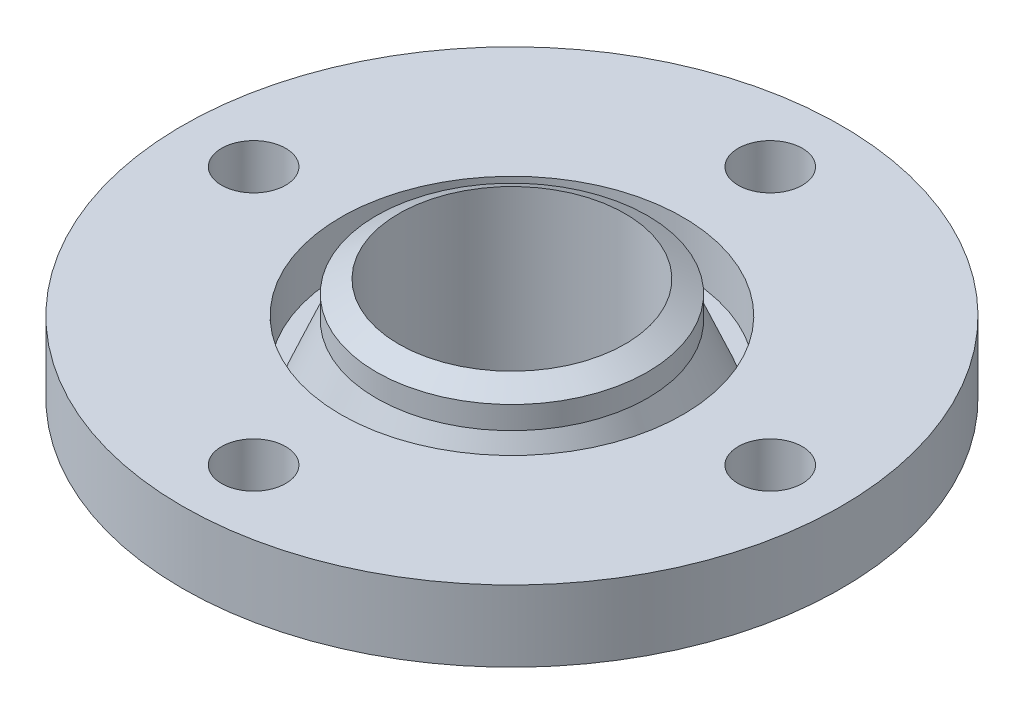
SolidWorks part; units mm, degrees
revolve "基体-旋转" add sketch "1" angle 360 about L0
sketch "1" plane through (0, 0, 0) normal (0, 0, 1) x (1, 0, 0)
  line L0 (0, 0) -> (0, -80.3134) construction
  line L1 (-31.75, 0) -> (-31.75, -45)
  line L2 (-31.75, -45) -> (-59, -45)
  line L3 (-59, -45) -> (-59, -29)
  line L4 (-59, -29) -> (-92.5, -29)
  line L5 (-92.5, -29) -> (-92.5, -9)
  line L6 (-92.5, -9) -> (-48, -9)
  line L7 (-48, -9) -> (-48, -23)
  line L8 (-48, -23) -> (-54, -29)
  line L9 (-54, -29) -> (-46, -29)
  line L10 (-46, -29) -> (-38.05, -10)
  line L11 (-38.05, -10) -> (-38.05, -3.6373)
  line L12 (92.5, -29) -> (92.5, -9) construction
  line L13 (59, -45) -> (59, -29) construction
  line L14 (-38.05, -3.6373) -> (-31.75, 0)
  line L15 (38.05, -10) -> (38.05, -3.6373) construction
  line L16 (46, -29) -> (38.05, -10) construction
  line L17 (48, -9) -> (48, -23) construction
  dimension "A1" = 76.1
  dimension "B1" = 96
  dimension "C" = 20
  dimension "DD" = 118
  dimension "D" = 185
  dimension "F" = 16
  dimension "D7" = 45
  dimension "E" = 6
  dimension "S" = 6.3
  dimension "H1" = 10
  dimension "D11" = 60
  dimension "H" = 45
  dimension "N1" = 92
ref_plane "前视" through (0, 0, 0) normal (0, 0, 1) x (1, 0, 0)
ref_plane "上视" through (0, 0, 0) normal (0, 1, 0) x (1, 0, 0)
ref_plane "右视" through (0, 0, 0) normal (1, 0, 0) x (0, 0, -1)
sketch "2" plane through (0, 0, 0) normal (0, 0, 1) x (1, 0, 0)
  line L0 (-72.5, 10.8054) -> (-72.5, -113.5815) construction
  line L1 (-72.5, -8) -> (-72.5, -30)
  line L2 (-81.5, -8) -> (-72.5, -8)
  line L3 (-81.5, -8) -> (-81.5, -30)
  line L4 (-81.5, -30) -> (-72.5, -30)
  line L5 (92.5, -9) -> (-92.5, -9) construction
  line L6 (-92.5, -29) -> (92.5, -29) construction
  line L7 (-63.5, -8) -> (-63.5, -30) construction
  line L8 (136.4663, 185.4534) -> (135.3473, 181.6131) construction
  line L9 (0, 62.8551) -> (0, -106.7074) construction
  line L10 (72.5, 10.8054) -> (72.5, -113.5815) construction
  dimension "D2" = 1
  dimension "D3" = 1
  dimension "L" = 18
  dimension "K" = 145
revolve "切除-旋转1" cut sketch "2" angle 360 about L0
ref_axis "基准轴1" through (0, -29, 0) along (0, 1, 0)
pattern_circular "阵列" count 4 over 360 about axis through (0, 0, 0) along (0, -1, 0) of "切除-旋转1"
equation "\"D1@阵列\"=\"n@2\""
